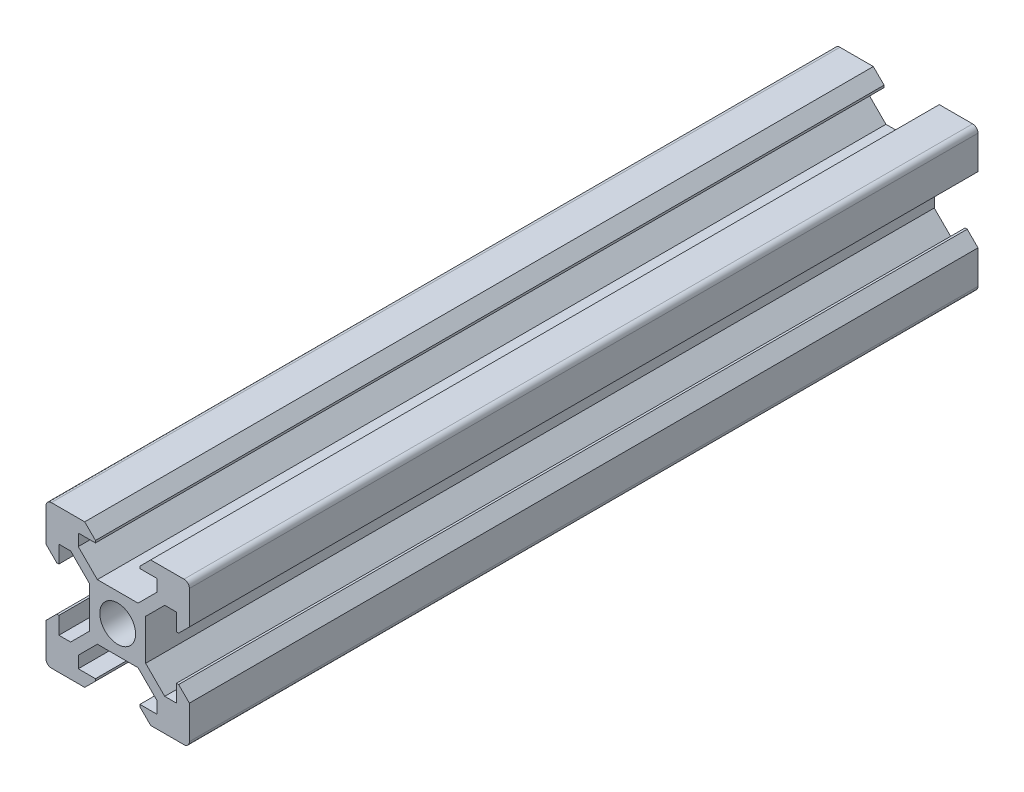
SolidWorks part; units mm, degrees
ref_plane "Alzado" through (0, 0, 0) normal (0, 0, 1) x (1, 0, 0)
ref_plane "Planta" through (0, 0, 0) normal (0, 1, 0) x (1, 0, 0)
ref_plane "Vista lateral" through (0, 0, 0) normal (1, 0, 0) x (0, 0, -1)
sketch "Croquis1" plane through (0, 0, 0) normal (0, 0, 1) x (1, 0, 0)
  line L0 (-4.6, 10) -> (-3.1, 8.5)
  line L3 (-4.6, 10) -> (-9.25, 10)
  line L5 (-3.1, 8.5) -> (-3.1, 8.2)
  line L6 (-3.1, 8.2) -> (-5.5, 8.2)
  line L7 (-5.5, 8.2) -> (-5.5, 6.5607)
  line L8 (-5.5, 6.5607) -> (-2.84, 3.9007)
  line L9 (-2.84, 3.9007) -> (0, 3.9007)
  line L10 (0, 0) -> (-15.3499, 15.3499) construction
  line L11 (-3.9007, 2.84) -> (-3.9007, 0)
  line L12 (-6.5607, 5.5) -> (-3.9007, 2.84)
  line L13 (-8.2, 5.5) -> (-6.5607, 5.5)
  line L14 (-8.2, 3.1) -> (-8.2, 5.5)
  line L15 (-8.5, 3.1) -> (-8.2, 3.1)
  line L16 (-10, 4.6) -> (-10, 9.25)
  line L17 (-10, 4.6) -> (-8.5, 3.1)
  line L18 (10, 4.6) -> (8.5, 3.1)
  line L19 (10, 4.6) -> (10, 9.25)
  line L20 (8.5, 3.1) -> (8.2, 3.1)
  line L21 (8.2, 3.1) -> (8.2, 5.5)
  line L22 (8.2, 5.5) -> (6.5607, 5.5)
  line L23 (6.5607, 5.5) -> (3.9007, 2.84)
  line L24 (3.9007, 2.84) -> (3.9007, 0)
  line L25 (5.5, 6.5607) -> (2.84, 3.9007)
  line L26 (5.5, 8.2) -> (5.5, 6.5607)
  line L27 (3.1, 8.2) -> (5.5, 8.2)
  line L28 (3.1, 8.5) -> (3.1, 8.2)
  line L29 (4.6, 10) -> (9.25, 10)
  line L30 (4.6, 10) -> (3.1, 8.5)
  line L31 (2.84, 3.9007) -> (0, 3.9007)
  line L32 (4.6, -10) -> (3.1, -8.5)
  line L33 (4.6, -10) -> (9.25, -10)
  line L34 (3.1, -8.5) -> (3.1, -8.2)
  line L35 (3.1, -8.2) -> (5.5, -8.2)
  line L36 (5.5, -8.2) -> (5.5, -6.5607)
  line L37 (5.5, -6.5607) -> (2.84, -3.9007)
  line L38 (2.84, -3.9007) -> (0, -3.9007)
  line L39 (6.5607, -5.5) -> (3.9007, -2.84)
  line L40 (8.2, -5.5) -> (6.5607, -5.5)
  line L41 (8.2, -3.1) -> (8.2, -5.5)
  line L42 (8.5, -3.1) -> (8.2, -3.1)
  line L43 (10, -4.6) -> (10, -9.25)
  line L44 (10, -4.6) -> (8.5, -3.1)
  line L45 (3.9007, -2.84) -> (3.9007, 0)
  line L46 (-10, -4.6) -> (-8.5, -3.1)
  line L47 (-10, -4.6) -> (-10, -9.25)
  line L48 (-8.5, -3.1) -> (-8.2, -3.1)
  line L49 (-8.2, -3.1) -> (-8.2, -5.5)
  line L50 (-8.2, -5.5) -> (-6.5607, -5.5)
  line L51 (-6.5607, -5.5) -> (-3.9007, -2.84)
  line L52 (-3.9007, -2.84) -> (-3.9007, 0)
  line L53 (-5.5, -6.5607) -> (-2.84, -3.9007)
  line L54 (-5.5, -8.2) -> (-5.5, -6.5607)
  line L55 (-3.1, -8.2) -> (-5.5, -8.2)
  line L56 (-3.1, -8.5) -> (-3.1, -8.2)
  line L57 (-4.6, -10) -> (-9.25, -10)
  line L58 (-4.6, -10) -> (-3.1, -8.5)
  line L59 (-2.84, -3.9007) -> (0, -3.9007)
  circle A0 centre (0, 0) radius 2.5
  arc A1 (-9.25, 10) -> (-10, 9.25) centre (-9.25, 9.25) ccw
  arc A2 (10, 9.25) -> (9.25, 10) centre (9.25, 9.25) ccw
  arc A3 (9.25, -10) -> (10, -9.25) centre (9.25, -9.25) ccw
  arc A4 (-10, -9.25) -> (-9.25, -10) centre (-9.25, -9.25) ccw
  point P18 (-10, 10)
  point P37 (10, 10)
  point P55 (10, -10)
  point P73 (-10, -10)
  point P79 (0, 0)
  dimension "D1" = 5
  dimension "D5" = 0.75
  dimension "D2" = 10
  dimension "D3" = 10
  dimension "D4" = 4.6
  dimension "D6" = 5.5
  dimension "D7" = 135
  dimension "D8" = 0.75
  dimension "D9" = 225
  dimension "D10" = 2.84
  dimension "D11" = 1.8
  dimension "D12" = 3.1
  dimension "D13" = 4
extrude "Saliente-Extruir1" add sketch "Croquis1" along normal blind 110
sketch "Sketch1" plane through (0, 0, 0) normal (1, 0, 0) x (0, 0, -1)
  line L0 (310, 59.3377) -> (310, -59.7305) construction
  line L1 (-310, -10.0996) -> (310, -10.0996)
  line L2 (-310, -10.0996) -> (-310, 10.0996)
  line L3 (-310, 10.0996) -> (310, 10.0996)
  line L4 (310, -10.0996) -> (310, 10.0996)
  line L5 (-310, -10.0996) -> (310, 10.0996) construction
  line L6 (-310, 10.0996) -> (310, -10.0996) construction
  line L7 (-110, -2.84) -> (-110, 2.84) construction
  point P0 (0, 0)
  dimension "D1" = 420
extrude "Cut-Extrude1" cut sketch "Sketch1" against normal blind 54 and the other way blind 46 rebuild error yes
